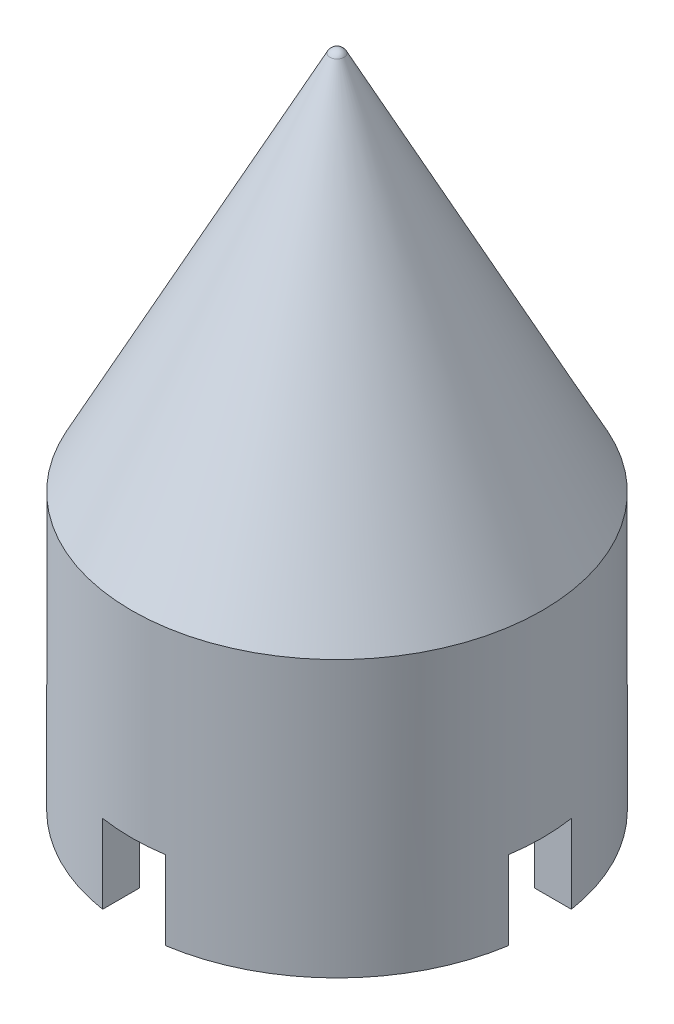
SolidWorks part; units mm, degrees
note: The reader was unsure of these and kept them because the rebuilt part matched: shared geometry of "Sketch1<2>", "Sketch1<3>".
ref_plane "Front Plane" through (0, 0, 0) normal (0, 0, 1) x (1, 0, 0)
ref_plane "Top Plane" through (0, 0, 0) normal (0, 1, 0) x (1, 0, 0)
ref_plane "Right Plane" through (0, 0, 0) normal (1, 0, 0) x (0, 0, -1)
sketch "Sketch1" plane through (0, 0, 0) normal (0, 1, 0) x (1, 0, 0)
  circle A0 centre (0, 0) radius 8.575
  circle A1 centre (0, 0) radius 10.425
  dimension "D1" = 17.15
  dimension "D2" = 1.85
extrude "Boss-Extrude1" add sketch "Sketch1" along normal blind 14
extrude "Boss-Extrude2" add sketch "Sketch1<2>" along normal blind 14 contours A0
sketch "Sketch1<2>" plane through (0, 0, 0) normal (0, 1, 0) x (1, 0, 0) same geometry as "Sketch1"
extrude "Cut-Extrude1" cut sketch "Sketch1<3>" along normal blind 4 contours A0
sketch "Sketch1<3>" plane through (0, 0, 0) normal (0, 1, 0) x (1, 0, 0) same geometry as "Sketch1"
sketch "Sketch2" plane through (0, 4, 0) normal (0, -1, 0) x (1, 0, 0)
  line L0 (0, 10.9637) -> (0, -11.2583) construction
  line L1 (-10.9023, 0) -> (11.025, 0) construction
  line L2 (-1.6, 10.9637) -> (-1.6, -11.2583)
  line L3 (1.6, 10.9637) -> (1.6, -11.2583)
  line L4 (-1.6, 10.9637) -> (1.6, 10.9637)
  line L5 (-1.817, -11.2583) -> (1.6, -11.2583)
  line L7 (-1.817, -9.6583) -> (0, -9.6583) construction
  line L10 (-10.9023, -1.6) -> (11.025, -1.6)
  line L11 (-1.817, -9.6583) -> (-1.6, -9.6583)
  line L12 (0, 9.3637) -> (0, -9.6583)
  line L13 (0, 9.3637) -> (0, 9.3637)
  line L14 (0, 9.3637) -> (0, -11.2583)
  line L15 (-10.9023, 1.6) -> (11.025, 1.6)
  line L16 (-10.9023, 1.6) -> (-10.9023, -1.6)
  line L17 (11.025, 1.6) -> (11.025, -1.6)
  dimension "D1" = 1.6
  dimension "D2" = 1.6
  dimension "D3" = 1.6
  dimension "D4" = 1.6
extrude "Cut-Extrude3" cut sketch "Sketch2" along normal blind 4
sketch "Sketch4" plane through (0, 0, 0) normal (1, 0, 0) x (0, 0, -1)
  line L2 (0, 14) -> (0, -11.6784) construction
  line L4 (0.3649, 33.3) -> (10.425, 14)
  line L6 (0, 14) -> (0, 33.5213)
  line L7 (0, 14) -> (10.425, 14)
  arc A0 (0, 33.5213) -> (0.3649, 33.3) centre (0, 33.1098) cw
  point P1 (0, 0)
  point P2 (0, 0)
  point P6 (0, 0)
  point P7 (0, 0)
  point P8 (0, 0)
  point P10 (0.3649, 33.3)
  point P15 (0, 0)
  point P16 (0, 0)
revolve "Revolve4" add sketch "Sketch4" angle 360 about L6
